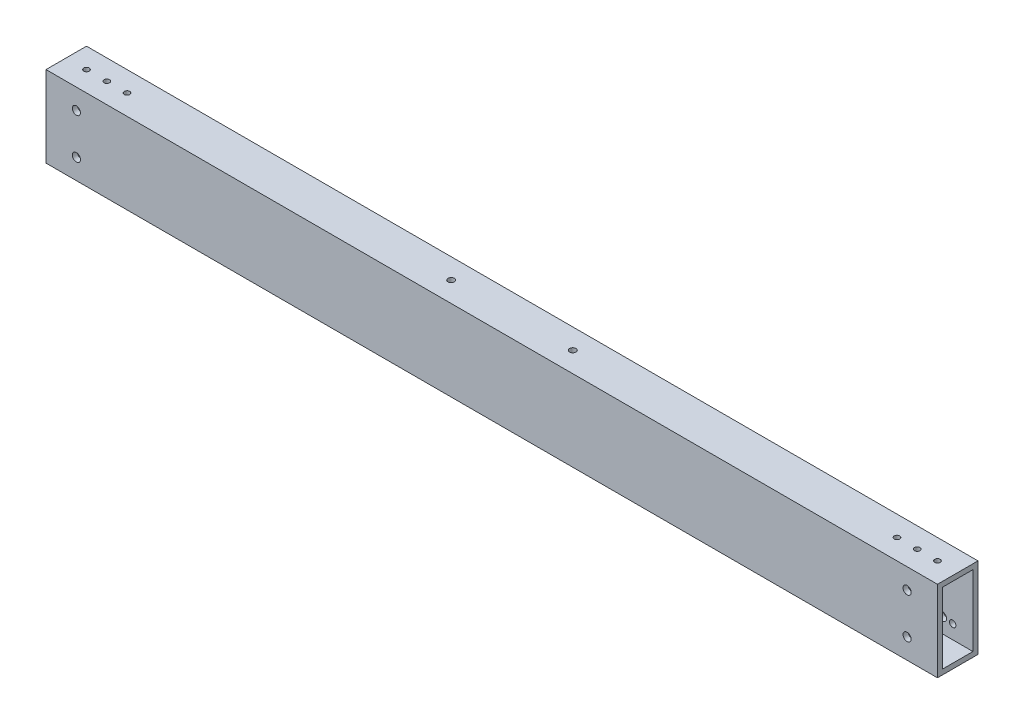
SolidWorks part; units mm, degrees
material "6061-T6 (SS)"
ref_plane "Front Plane" through (0, 0, 0) normal (0, 0, 1) x (1, 0, 0)
ref_plane "Top Plane" through (0, 0, 0) normal (0, 1, 0) x (1, 0, 0)
ref_plane "Right Plane" through (0, 0, 0) normal (1, 0, 0) x (0, 0, -1)
sketch "Sketch1" plane through (0, 0, 0) normal (0, 0, 1) x (1, 0, 0)
  line L1 (-279.4, 25.4) -> (279.4, 25.4)
  line L2 (-279.4, 25.4) -> (-279.4, -25.4)
  line L3 (-279.4, -25.4) -> (279.4, -25.4)
  line L4 (279.4, 25.4) -> (279.4, -25.4)
  line L5 (-279.4, 25.4) -> (279.4, -25.4) construction
  line L6 (-279.4, -25.4) -> (279.4, 25.4) construction
  point P0 (0, 0)
  dimension "D1" = 50.8
  dimension "D2" = 558.8
extrude "Boss-Extrude1" add sketch "Sketch1" along normal mid plane 25.4
sketch "Sketch2" plane through (279.4, 0, 0) normal (1, 0, 0) x (0, 0, -1)
  line L8 (9.525, -22.225) -> (9.525, 22.225)
  line L9 (9.525, 22.225) -> (-9.525, 22.225)
  line L10 (-9.525, 22.225) -> (-9.525, -22.225)
  line L11 (-9.525, -22.225) -> (9.525, -22.225)
  line L12 (9.525, -22.225) -> (9.525, 22.225)
  line L13 (9.525, 22.225) -> (-9.525, 22.225)
  line L14 (-9.525, 22.225) -> (-9.525, -22.225)
  line L15 (-9.525, -22.225) -> (9.525, -22.225)
  dimension "D1" = 3.175
extrude "Cut-Extrude1" cut sketch "Sketch2" against normal through all
sketch "Sketch3" plane through (0, 0, 12.7) normal (0, 0, 1) x (1, 0, 0)
sketch "Sketch4" plane through (0, 25.4, 0) normal (0, 1, 0) x (1, 0, 0)
  line L0 (-279.4, -12.7) -> (-279.4, 12.7) construction
  line L1 (0, -12.7) -> (0, 12.7) construction
  line L2 (279.4, -12.7) -> (-279.4, -12.7) construction
  line L3 (279.4, 12.7) -> (-279.4, 12.7) construction
  circle A0 centre (-304.8, 0) radius 1.7272
  circle A1 centre (-292.1, 0) radius 1.7272
  circle A3 centre (-266.7, 0) radius 1.7272
  circle A4 centre (-254, 0) radius 1.7272
  circle A5 centre (-241.3, 0) radius 1.7272
  circle A7 centre (241.3, 0) radius 1.7272
  circle A8 centre (254, 0) radius 1.7272
  circle A9 centre (266.7, 0) radius 1.7272
  circle A12 centre (-279.4, 0) radius 1.7272 [skipped]
  circle A14 centre (-228.6, 0) radius 1.7272 [skipped]
  dimension "D2" = 3.4544
  dimension "D3" = 7
  dimension "D4" = 12.7
extrude "Cut-Extrude2" cut sketch "Sketch4" against normal blind 6.35
hole_wizard "1/4-20 Tapped Hole1" positions "Sketch8" profile "Sketch7" tap size "1/4-20" standard "ANSI Inch" end condition through all
sketch "Sketch8" plane through (0, 0, 12.7) normal (0, 0, 1) x (1, 0, 0)
  line L0 (-279.4, 25.4) -> (-279.4, -25.4) construction
  line L1 (279.4, -25.4) -> (279.4, 25.4) construction
  line L2 (-279.4, -25.4) -> (279.4, -25.4) construction
  point P0 (-260.35, 12.7)
  point P2 (-260.35, -12.7)
  point P4 (260.35, 12.7)
  point P6 (260.35, -12.7)
  dimension "D1" = 25.4
  dimension "D2" = 19.05
  dimension "D3" = 25.4
  dimension "D4" = 19.05
  dimension "D5" = 12.7
  dimension "D6" = 12.7
sketch "Sketch7" plane through (-260.35, 12.7, 12.7) normal (1, 0, 0) x (0, -1, 0)
  line L0 (0, 0) -> (0, 25.4)
  line L1 (0, 25.4) -> (2.5527, 25.4)
  line L2 (2.5527, 25.4) -> (2.5527, 0)
  line L5 (2.5527, 0) -> (0, 0)
  line L11 (0, -6.35) -> (0, 107.95) construction
  dimension "Thread Major Dia." = 5.1054
  dimension "Thru Tap Drill Depth" = 25.4
hole_wizard "#10-32 Tapped Hole1" positions "Sketch10" profile "Sketch9" tap size "#10-32" standard "ANSI Inch"
sketch "Sketch10" plane through (0, 0, -12.7) normal (0, 0, -1) x (-1, 0, 0)
  line L0 (-279.4, 25.4) -> (279.4, 25.4) construction
  line L1 (-279.4, -25.4) -> (-279.4, 25.4) construction
  point P0 (-266.7, -13.4937)
  point P15 (-190.5, -13.4937)
  point P16 (-114.3, -13.4937)
  point P17 (-38.1, -13.4937)
  point P18 (38.1, -13.4937)
  point P19 (114.3, -13.4937)
  point P20 (190.5, -13.4937)
  point P21 (266.7, -13.4937)
  dimension "D1" = 76.2
  dimension "D2" = 38.8937
  dimension "D3" = 12.7
  dimension "D5" = 8
sketch "Sketch9" plane through (266.7, -13.4937, -12.7) normal (1, 0, 0) x (0, 1, 0)
  line L0 (0, 0) -> (0, 6.2933)
  line L1 (0, 6.2933) -> (2.0193, 5.08)
  line L2 (2.0193, 5.08) -> (2.0193, 0)
  line L5 (2.0193, 0) -> (0, 0)
  line L10 (0, 6.2933) -> (-2.0193, 5.08) construction
  line L11 (0, -6.35) -> (0, 107.95) construction
  dimension "Tap Drill Dia." = 4.0386
  dimension "Tap Drill Depth" = 5.08
  dimension "Drill Angle" = 118
hole_wizard "5/32 (0.15625) Diameter Hole1" positions "Sketch12" profile "Sketch11" hole size "5/32" standard "ANSI Inch" end condition through all
sketch "Sketch12" plane through (0, 25.4, 0) normal (0, 1, 0) x (1, 0, 0)
  line L2 (-38.1, 0) -> (38.1, 0) construction
  point P0 (-38.1, 0)
  point P2 (38.1, 0)
  dimension "D1" = 76.2
sketch "Sketch11" plane through (-38.1, 25.4, 0) normal (1, 0, 0) x (0, 0, 1)
  line L0 (0, 0) -> (0, 50.8)
  line L1 (0, 50.8) -> (1.9844, 50.8)
  line L2 (1.9844, 50.8) -> (1.9844, 0)
  line L5 (1.9844, 0) -> (0, 0)
  line L11 (0, -6.35) -> (0, 107.95) construction
  dimension "Thru Hole Dia." = 3.9688
  dimension "Thru Hole Depth" = 50.8
